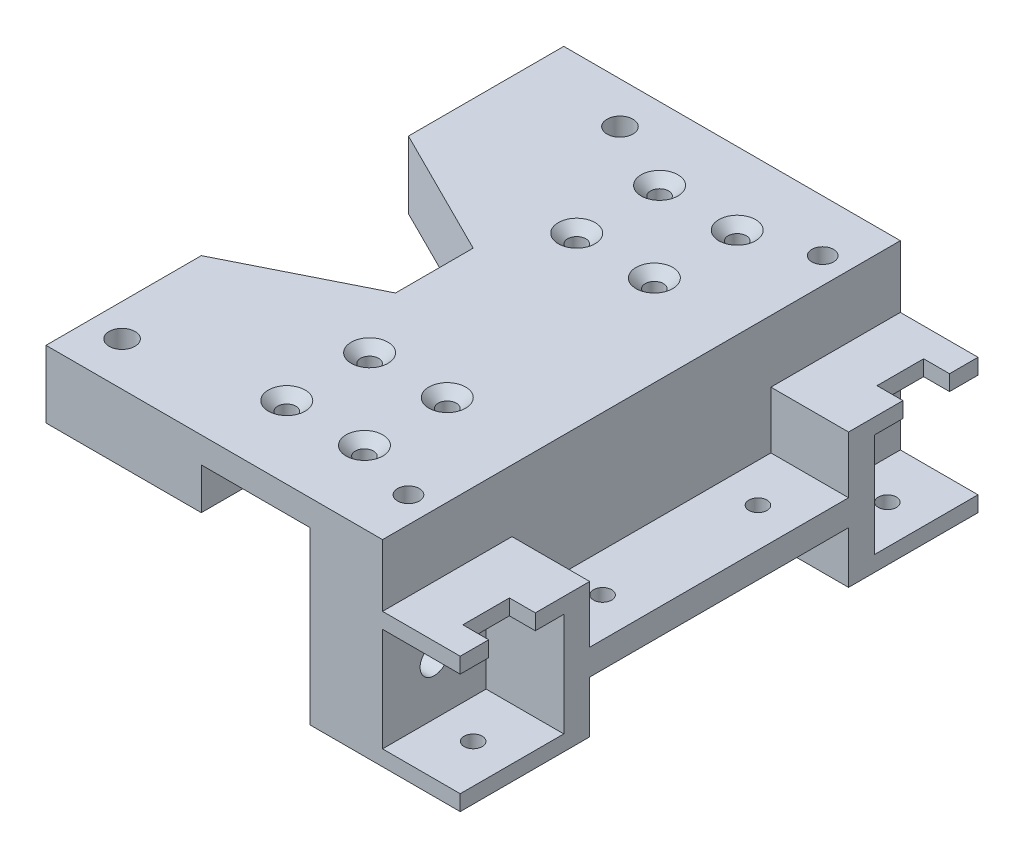
SolidWorks part; units mm, degrees
ref_plane "Front Plane" through (0, 0, 0) normal (0, 0, 1) x (1, 0, 0)
ref_plane "Top Plane" through (0, 0, 0) normal (0, 1, 0) x (1, 0, 0)
ref_plane "Right Plane" through (0, 0, 0) normal (1, 0, 0) x (0, 0, -1)
sketch "Sketch1" plane through (0, 0, 0) normal (0, 1, 0) x (1, 0, 0)
  line L0 (0, 50) -> (0, -50) construction
  line L1 (-10, 50) -> (10, 50)
  line L2 (-10, 50) -> (-10, -50)
  line L3 (-10, -50) -> (10, -50)
  line L4 (10, 50) -> (10, -50) construction
  line L5 (-10, 50) -> (10, -50) construction
  line L6 (-10, -50) -> (10, 50) construction
  line L7 (-7.5, 36) -> (7.5, 36) construction
  line L8 (-7.5, 36) -> (7.5, 20) construction
  line L9 (-10, 0) -> (10, 0) construction
  line L10 (-7.5, -36) -> (7.5, -20) construction
  line L11 (-7.5, -36) -> (7.5, -36) construction
  line L12 (-7.5, 20) -> (7.5, 20) construction
  line L13 (10, 50) -> (11, 50)
  line L14 (11, 50) -> (11, -50)
  line L15 (11, -50) -> (10, -50)
  circle A0 centre (-7.5, 36) radius 1.75
  circle A1 centre (7.5, 36) radius 1.75
  circle A2 centre (-7.5, 20) radius 1.75
  circle A3 centre (7.5, 20) radius 1.75
  circle A4 centre (7.5, -20) radius 1.75
  circle A5 centre (-7.5, -20) radius 1.75
  circle A6 centre (7.5, -36) radius 1.75
  circle A7 centre (-7.5, -36) radius 1.75
  point P0 (0, 0)
  point P16 (0, 36)
  dimension "D2" = 3.5
  dimension "D1" = 20
  dimension "D3" = 15
  dimension "D4" = 16
  dimension "D5" = 100
  dimension "D6" = 20
  dimension "D7" = 1
extrude "Boss-Extrude1" add sketch "Sketch1" along normal blind 5
sketch "Sketch2" plane through (11, 0, 0) normal (1, 0, 0) x (0, 0, -1)
  line L1 (-50, 5) -> (50, 5)
  line L2 (-50, 5) -> (-50, -33)
  line L3 (-50, -33) -> (50, -33)
  line L5 (50, 5) -> (50, -33)
  line L6 (50, 5) -> (50, 0) construction
  line L7 (-50, 5) -> (-50, 0) construction
  line L8 (-50, 5) -> (50, 5) construction
  dimension "D1" = 38
extrude "Boss-Extrude2" add sketch "Sketch2" along normal blind 14
sketch "Sketch3" plane through (25, 0, 0) normal (1, 0, 0) x (0, 0, -1)
  line L0 (0, 5) -> (0, -33) construction
  line L1 (-25, -18) -> (25, -18)
  line L2 (-25, -18) -> (-25, -23)
  line L3 (-25, -23) -> (25, -23)
  line L4 (25, -18) -> (25, -23)
  line L5 (50, 5) -> (-50, 5) construction
  line L6 (-50, -33) -> (50, -33) construction
  point P10 (0, -18)
  dimension "D1" = 5
  dimension "D2" = 50
  dimension "D3" = 10
extrude "Boss-Extrude3" add sketch "Sketch3" along normal blind 15
sketch "Sketch4" plane through (0, -18, 0) normal (0, 1, 0) x (1, 0, 0)
  line L0 (25, 0) -> (40, 0) construction
  line L1 (25, 25) -> (25, -25) construction
  line L2 (40, 25) -> (40, -25) construction
  line L3 (32.5, -15) -> (32.5, 15) construction
  circle A0 centre (32.5, 15) radius 1.75
  circle A1 centre (32.5, -15) radius 1.75
  point P8 (32.5, 0)
  dimension "D1" = 30
  dimension "D2" = 3.5
extrude "Cut-Extrude1" cut sketch "Sketch4" against normal through all
sketch "Sketch8" plane through (25, 0, 0) normal (1, 0, 0) x (0, 0, -1)
  line L0 (-50, 5) -> (-50, -33) construction
  line L1 (-50, -7) -> (-25, -7)
  line L2 (-50, -7) -> (-50, -10)
  line L3 (-50, -33) -> (-25, -33)
  line L4 (-25, -7) -> (-25, -33)
  line L5 (-50, -30) -> (-50, -33)
  line L6 (-50, -30) -> (-30, -30)
  line L8 (-50, -10) -> (-30, -10)
  line L9 (-30, -30) -> (-30, -10)
  line L10 (0, 19.25) -> (0, -19.25) construction
  line L11 (30, -30) -> (30, -10)
  line L12 (50, -10) -> (30, -10)
  line L13 (50, -30) -> (30, -30)
  line L14 (50, -30) -> (50, -33)
  line L15 (25, -7) -> (25, -33)
  line L16 (50, -33) -> (25, -33)
  line L17 (50, -7) -> (50, -10)
  line L18 (50, -7) -> (25, -7)
  line L19 (-50, -33) -> (50, -33) construction
  dimension "D1" = 3
  dimension "D2" = 5
  dimension "D3" = 3
  dimension "D4" = 20
  dimension "D5" = 20
extrude "Boss-Extrude6" add sketch "Sketch8" along normal blind 15
sketch "Sketch9" plane through (25, 0, 0) normal (1, 0, 0) x (0, 0, -1)
  line L0 (-50, -10) -> (-30, -30) construction
  line L1 (50, -10) -> (30, -30) construction
  circle A0 centre (-40, -20) radius 2.75
  circle A1 centre (40, -20) radius 2.75
  dimension "D1" = 5.5
extrude "Cut-Extrude3" cut sketch "Sketch9" against normal through all
sketch "Sketch10" plane through (11, 0, 0) normal (-1, 0, 0) x (0, 0, 1)
  circle A0 centre (-40, -20) radius 4.5
  circle A1 centre (40, -20) radius 4.5
  dimension "D1" = 9
extrude "Cut-Extrude4" cut sketch "Sketch10" against normal offset from surface (9 mm away) 5 up to face at (25, -20, 37.25)
sketch "Sketch11" plane through (0, -7, 0) normal (0, 1, 0) x (1, 0, 0)
  line L0 (40, -25) -> (40, -50) construction
  line L1 (40, -35.5) -> (35, -35.5)
  line L2 (40, -35.5) -> (40, -44.5)
  line L3 (40, -44.5) -> (35, -44.5)
  line L4 (35, -35.5) -> (35, -44.5)
  line L5 (35, -40) -> (40, -40) construction
  line L6 (40, -50) -> (25, -50) construction
  line L7 (-10, 0) -> (40, 0) construction
  line L8 (-10, 50) -> (-10, -50) construction
  line L9 (40, 25) -> (40, -25) construction
  line L10 (40, -35.5) -> (35, -35.5)
  line L11 (40, -44.5) -> (35, -44.5)
  line L12 (35, 40) -> (40, 40) construction
  line L13 (40, 44.5) -> (35, 44.5)
  line L14 (40, 35.5) -> (35, 35.5)
  line L15 (35, 35.5) -> (35, 44.5)
  line L16 (40, 44.5) -> (35, 44.5)
  line L17 (40, 35.5) -> (40, 44.5)
  line L18 (40, 35.5) -> (35, 35.5)
  line M7 (40, -50) -> (40, -25)
  dimension "D1" = 9
  dimension "D2" = 10
  dimension "D3" = 5
extrude "Cut-Extrude5" cut sketch "Sketch11" against normal up to next contours L1 L4 L3 M7 | L14 L17 L13 L15 region at (37.5, -7, 40) region at (37.5, -7, -40)
sketch "Sketch12" plane through (0, -30, 0) normal (0, 1, 0) x (1, 0, 0)
  line L0 (40, -40) -> (25, -40) construction
  line L1 (40, -30) -> (40, -50) construction
  line L2 (25, -25) -> (25, -50) construction
  line L3 (-19.25, 0) -> (19.25, 0) construction
  circle A0 centre (32.5, -40) radius 1.75
  circle A2 centre (32.5, 40) radius 1.75
  dimension "D1" = 3.5
extrude "Cut-Extrude6" cut sketch "Sketch12" against normal through all
sketch "Sketch13" plane through (-10, 0, 0) normal (-1, 0, 0) x (0, 0, 1)
  line L1 (-50, 5) -> (50, 5)
  line L2 (-50, 5) -> (-50, -8)
  line L3 (-50, -8) -> (50, -8)
  line L4 (50, 5) -> (50, -8)
  dimension "D1" = 13
extrude "Boss-Extrude7" add sketch "Sketch13" along normal blind 30
sketch "Sketch14" plane through (0, 5, 0) normal (0, 1, 0) x (1, 0, 0)
  line L0 (25, 50) -> (-40, 50) construction
  line L5 (-40, -50) -> (25, -50) construction
  line L6 (-27.65, 42) -> (-27.65, -41.58) construction
  line L7 (-40, -50) -> (-40, 50) construction
  line L12 (-21.15, 35.5) -> (40, 35.5) construction
  line L18 (-33.73, -35.5) -> (40, -35.5) construction
  circle A0 centre (-21.15, 42) radius 2.5
  circle A1 centre (-33.73, -41.58) radius 2.5
  circle A2 centre (-33.73, -41.58) radius 6.08 construction
  circle A3 centre (-21.15, 42) radius 6.5 construction
  point P4 (40, -35.5)
  point P10 (0, 0)
  point P13 (0, 0)
  point P14 (0, 0)
  point P19 (0, 0)
  point P22 (0, 0)
  dimension "D1" = 5
  dimension "D2" = 5
  dimension "D4" = 12.16
  dimension "D5" = 13
  dimension "D3" = 21.15
extrude "Cut-Extrude7" cut sketch "Sketch14" against normal through all
sketch "Sketch15" plane through (0, -8, 0) normal (0, -1, 0) x (1, 0, 0)
  line L0 (-40, -50) -> (-40, 50) construction
  line L1 (-29.63, 43.9471) -> (-33.73, 46.3143)
  line L2 (-33.73, 46.3143) -> (-37.83, 43.9471)
  line L3 (-37.83, 43.9471) -> (-37.83, 39.2129)
  line L4 (-37.83, 39.2129) -> (-33.73, 36.8457)
  line L5 (-33.73, 36.8457) -> (-29.63, 39.2129)
  line L6 (-29.63, 39.2129) -> (-29.63, 43.9471)
  line L7 (-17.05, -44.3671) -> (-17.05, -39.6329)
  line L8 (-17.05, -39.6329) -> (-21.15, -37.2657)
  line L9 (-21.15, -37.2657) -> (-25.25, -39.6329)
  line L10 (-25.25, -39.6329) -> (-25.25, -44.3671)
  line L11 (-25.25, -44.3671) -> (-21.15, -46.7343)
  line L12 (-21.15, -46.7343) -> (-17.05, -44.3671)
  circle A0 centre (-33.73, 41.58) radius 4.1 construction
  circle A1 centre (-21.15, -42) radius 4.1 construction
  dimension "D1" = 8.2
extrude "Cut-Extrude8" cut sketch "Sketch15" against normal blind 5
sketch "Sketch16" plane through (0, 5, 0) normal (0, 1, 0) x (1, 0, 0)
  line L0 (20, 40) -> (40, 40) construction
  line L1 (40, 40) -> (40, -40) construction
  line L2 (40, -40) -> (20, -40) construction
  line L3 (20, -40) -> (20, 40) construction
  line L4 (40, 50) -> (40, 30) construction
  line L5 (40, -30) -> (40, -50) construction
  circle A0 centre (20, 40) radius 2.1
  circle A1 centre (20, -40) radius 2.1
  point P6 (40, 40)
  point P9 (40, -40)
  dimension "D1" = 4.2
  dimension "D2" = 4.2
  dimension "D3" = 20
extrude "Cut-Extrude9" cut sketch "Sketch16" against normal blind 4
chamfer "Chamfer1" distance 1.8 angle 45 8 edges at (7.5, 5, 34.25) (-7.5, 5, 34.25) (7.5, 5, 18.25) (-7.5, 5, 18.25) (7.5, 5, -18.25) (-7.5, 5, -18.25) (7.5, 5, -34.25) (-7.5, 5, -34.25)
sketch "Sketch17" plane through (0, 5, 0) normal (0, 1, 0) x (1, 0, 0)
  line L0 (-40, 20) -> (-15, 7.5)
  line L1 (-40, -50) -> (-40, 50) construction
  line L2 (-15, 7.5) -> (-15, -7.5)
  line L3 (-15, -7.5) -> (-40, -20)
  line L4 (-40, -20) -> (-40, 20)
  point P5 (-15, 0)
  dimension "D1" = 15
  dimension "D2" = 25
  dimension "D3" = 40
extrude "Cut-Extrude10" cut sketch "Sketch17" against normal through all
